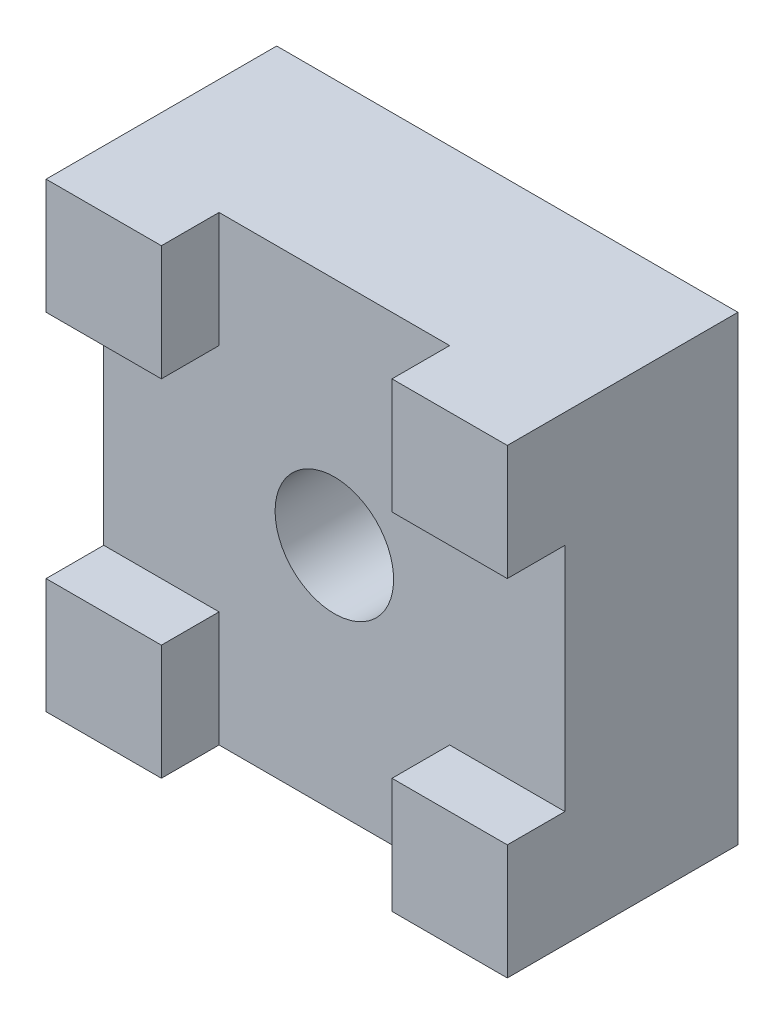
SolidWorks part; units mm, degrees
ref_plane "Front Plane" through (0, 0, 0) normal (1, 0, 0) x (0, 1, 0)
ref_plane "Top Plane" through (0, 0, 0) normal (0, 0, 1) x (0, 1, 0)
ref_plane "Right Plane" through (0, 0, 0) normal (0, 1, 0) x (-1, 0, 0)
sketch "Sketch1" plane through (0, 0, 0) normal (0, 0, 1) x (0, 1, 0)
  line L1 (-12.7, 12.7) -> (12.7, 12.7)
  line L2 (-12.7, 12.7) -> (-12.7, -12.7)
  line L3 (-12.7, -12.7) -> (12.7, -12.7)
  line L4 (12.7, 12.7) -> (12.7, -12.7)
  line L5 (-12.7, 12.7) -> (12.7, -12.7) construction
  line L6 (-12.7, -12.7) -> (12.7, 12.7) construction
  circle A0 centre (0, 0) radius 6.35
  circle A1 centre (0, 0) radius 3.2639
  point P0 (0, 0)
  dimension "D3" = 12.7
  dimension "D4" = 6.5278
  dimension "D1" = 25.4
  dimension "D2" = 25.4
extrude "Boss-Extrude1" add sketch "Sketch1" along normal blind 9.525 contours L1 L4 L3 L2
sketch "Sketch2" plane through (0, 0, 0) normal (0, 0, -1) x (1, 0, 0)
  circle A0 centre (0, 0) radius 6.35
  circle A1 centre (0, 0) radius 3.2639
  dimension "D1" = 12.7
  dimension "D2" = 6.5278
extrude "Cut-Extrude1" cut sketch "Sketch2" against normal blind 4.7752 contours A0
extrude "Cut-Extrude2" cut sketch "Sketch1<3>" along normal blind 9.525 contours A1 region at (0, 0, 0)
sketch "Sketch1<3>" plane through (0, 0, 0) normal (0, 0, 1) x (0, 1, 0) same geometry as "Sketch1"
sketch "Sketch3" plane through (0, 0, 9.525) normal (0, 0, 1) x (1, 0, 0)
  line L0 (-12.7, 12.7) -> (12.7, 12.7) construction
  line L1 (12.7, -12.7) -> (12.7, 12.7) construction
  line L2 (-12.7, -12.7) -> (12.7, -12.7) construction
  line L3 (-12.7, -12.7) -> (-12.7, 12.7) construction
  line L5 (-12.7, 12.7) -> (-6.35, 12.7)
  line L6 (-12.7, 12.7) -> (-12.7, 6.35)
  line L7 (-12.7, 6.35) -> (-6.35, 6.35)
  line L8 (-6.35, 12.7) -> (-6.35, 6.35)
  line L9 (-12.7, -6.35) -> (-6.35, -6.35)
  line L10 (-12.7, -6.35) -> (-12.7, -12.7)
  line L11 (-12.7, -12.7) -> (-6.35, -12.7)
  line L12 (-6.35, -6.35) -> (-6.35, -12.7)
  line L13 (12.7, -12.7) -> (6.35, -12.7)
  line L14 (12.7, -12.7) -> (12.7, -6.35)
  line L15 (12.7, -6.35) -> (6.35, -6.35)
  line L16 (6.35, -12.7) -> (6.35, -6.35)
  line L17 (6.35, 12.7) -> (12.7, 12.7)
  line L18 (6.35, 12.7) -> (6.35, 6.35)
  line L19 (6.35, 6.35) -> (12.7, 6.35)
  line L20 (12.7, 12.7) -> (12.7, 6.35)
  point P0 (0, 12.7)
  point P1 (-6.35, 12.7)
  point P4 (6.35, 12.7)
  point P5 (12.7, 0)
  point P6 (0, -12.7)
  point P9 (-12.7, 0)
  point P12 (-12.7, 6.35)
  point P15 (-12.7, -6.35)
  point P16 (-7.1747, -12.7)
  point P17 (8.2267, -12.7)
  point P18 (12.7, -6.35)
  point P19 (12.7, 6.35)
  dimension "D1" = 12.7
  dimension "D2" = 6.35
  dimension "D3" = 6.35
  dimension "D4" = 6.35
  dimension "D5" = 6.35
  dimension "D6" = 6.35
extrude "Boss-Extrude3" add sketch "Sketch3" along normal blind 3.175
